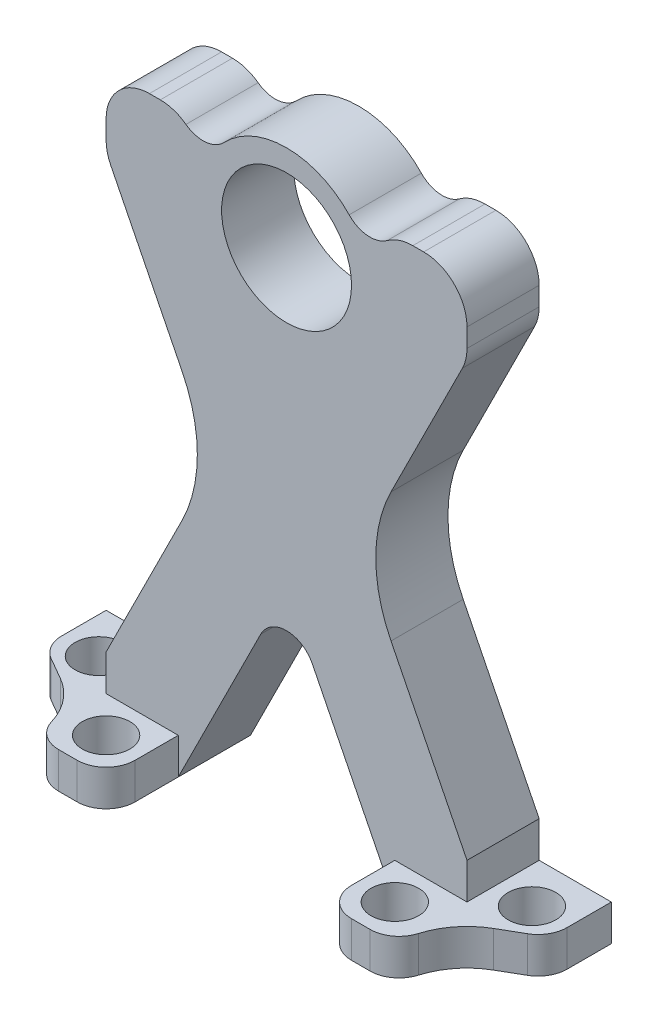
SolidWorks part; units mm, degrees
ref_plane "Front Plane" through (0, 0, 0) normal (0, 0, 1) x (1, 0, 0)
ref_plane "Top Plane" through (0, 0, 0) normal (0, 1, 0) x (1, 0, 0)
ref_plane "Right Plane" through (0, 0, 0) normal (1, 0, 0) x (0, 0, -1)
sketch "Sketch1" plane through (0, 0, 0) normal (0, 0, 1) x (1, 0, 0)
  line L0 (-7.5, 20) -> (-5.8703, 16.7407)
  line L1 (-12.5, -20) -> (-7.5, -20)
  line L2 (-12.5, -20) -> (-12.5, -15)
  line L3 (-12.5, 20) -> (-7.5, 20)
  line L4 (12.5, -20) -> (12.5, -15)
  line L5 (-3.9686, 20) -> (3.9686, 20)
  line L6 (7.5, 20) -> (12.5, 20)
  line L7 (12.5, 15) -> (12.5, 20)
  line L8 (5.8703, 16.7407) -> (7.5, 20)
  line L9 (12.5, -15) -> (5, 0)
  line L10 (5, 0) -> (12.5, 15)
  line L11 (7.5, -20) -> (12.5, -20)
  line L12 (7.5, -20) -> (0, -5)
  line L13 (0, -5) -> (-7.5, -20)
  line L14 (-12.5, 15) -> (-12.5, 20)
  line L15 (-12.5, -15) -> (-5, 0)
  line L16 (-5, 0) -> (-12.5, 15)
  circle A0 centre (0, 15.5) radius 4.5
  arc A1 (5.8703, 16.7407) -> (-5.8703, 16.7407) centre (0, 15.5) ccw
  point P0 (0, 0)
  dimension "D2" = 40
  dimension "D3" = 35.5
  dimension "D4" = 5
  dimension "D1" = 25
  dimension "D5" = 5
  dimension "D6" = 5
  dimension "D7" = 5
  dimension "D8" = 5
  dimension "D9" = 5
  dimension "D10" = 5
  dimension "D11" = 0
  dimension "D12" = 5
  dimension "D13" = 20
  dimension "D16" = 5
  dimension "D17" = 5
  dimension "D18" = 0
  dimension "D19" = 5
extrude "Boss-Extrude2" add sketch "Sketch1" along normal blind 5 contours L8 A1 L5 A0 L0 L3 L14 L16 L15 L2 L1 L13 L12 L11 L4 L9 L10 L7 L6 | L5 A1 region at (0, 0.8696, 0) region at (0, 20.6069, 0)
sketch "Sketch2" plane through (0, 0, 5) normal (0, 0, 1) x (1, 0, 0)
  line L0 (-12.5, -20) -> (-12.5, -15) construction
  line L1 (-7.5, -20) -> (-12.5, -20)
  line L2 (-7.5, -20) -> (-7.5, -17.5)
  line L3 (-7.5, -17.5) -> (-12.5, -17.5)
  line L4 (-12.5, -20) -> (-12.5, -17.5)
  line L5 (12.5, -20) -> (12.5, -15) construction
  line L6 (7.5, -20) -> (12.5, -20)
  line L7 (7.5, -20) -> (7.5, -17.5)
  line L8 (7.5, -17.5) -> (12.5, -17.5)
  line L9 (12.5, -20) -> (12.5, -17.5)
extrude "Boss-Extrude3" add sketch "Sketch2" along normal blind 10
sketch "Sketch3" plane through (12.5, 0, 0) normal (1, 0, 0) x (0, 0, -1)
  line L0 (-15, -17.5) -> (-5, -17.5) construction
  line L1 (0, -20) -> (-10, -20)
  line L2 (0, -20) -> (0, -17.5)
  line L3 (0, -17.5) -> (-10, -17.5)
  line L4 (-10, -20) -> (-10, -17.5)
extrude "Boss-Extrude4" add sketch "Sketch3" along normal blind 5
sketch "Sketch4" plane through (-12.5, 0, 0) normal (-1, 0, 0) x (0, 0, 1)
  line L0 (15, -17.5) -> (5, -17.5) construction
  line L1 (0, -20) -> (10, -20)
  line L2 (0, -20) -> (0, -17.5)
  line L3 (0, -17.5) -> (10, -17.5)
  line L4 (10, -20) -> (10, -17.5)
extrude "Boss-Extrude5" add sketch "Sketch4" along normal blind 5
sketch "Sketch5" plane through (0, -17.5, 0) normal (0, 1, 0) x (1, 0, 0)
  line L0 (-17.5, 0) -> (-12.5, 0) construction
  line L1 (-7.5, -15) -> (-12.5, -15) construction
  circle A0 centre (-15, -3) radius 1.65
  circle A1 centre (-10, -12) radius 1.65
  circle A2 centre (10, -12) radius 1.65
  circle A3 centre (15, -3) radius 1.65
  dimension "D1" = 3
  dimension "D2" = 3
extrude "Cut-Extrude1" cut sketch "Sketch5" against normal blind 5
chamfer "Chamfer1" distance 10 angle 30 2 edges at (17.5, -18.75, 10) (-17.5, -18.75, 10) first distance on face at (15, -18.75, 10) first distance on face at (-15, -18.75, 10)
fillet "Fillet1" radius 2 4 edges at (12.5, -18.75, 15) (7.5, -18.75, 15) (-7.5, -18.75, 15) (-12.5, -18.75, 15)
fillet "Fillet2" radius 5 2 edges at (12.5, -18.75, 7.1132) (-12.5, -18.75, 7.1132)
fillet "Fillet3" radius 2 2 edges at (17.5, -18.75, 4.2265) (-17.5, -18.75, 4.2265)
fillet "Fillet4" radius 2 3 edges at (-5.8703, 16.7407, 2.5) (5.8703, 16.7407, 2.5) (0, -5, 2.5)
fillet "Fillet5" radius 10 2 edges at (5, 0, 2.5) (-5, 0, 2.5)
fillet "Fillet6" radius 3 6 edges at (-7.5, 20, 2.5) (-12.5, 20, 2.5) (-12.5, 15, 2.5) (12.5, 15, 2.5) (7.5, 20, 2.5) (12.5, 20, 2.5)
sketch "Sketch6" plane through (0, -17.5, 0) normal (0, 1, 0) x (1, 0, 0)
  line L0 (-9.5, -15) -> (-10.5, -15) construction
  line L1 (10.5, -15) -> (9.5, -15) construction
  line L3 (-16.6955, -17.9546) -> (19.3779, -17.9546)
  line L4 (-16.6955, -17.9546) -> (-16.6955, -10)
  line L5 (-16.6955, -10) -> (19.3779, -10)
  line L6 (19.3779, -17.9546) -> (19.3779, -10)
  circle A0 centre (-10, -7.5) radius 1.65
  circle A1 centre (10, -7.5) radius 1.65
  point P4 (-10, -15)
  point P7 (10, -15)
  point P14 (-10, -15)
  dimension "D1" = 7.5
  dimension "D2" = 7.5
  dimension "D3" = 5
extrude "Cut-Extrude2" cut sketch "Sketch6" against normal blind 5
fillet "Fillet10" radius 2 4 edges at (12.5, -18.75, 10) (7.5, -18.75, 10) (-7.5, -18.75, 10) (-12.5, -18.75, 10)
